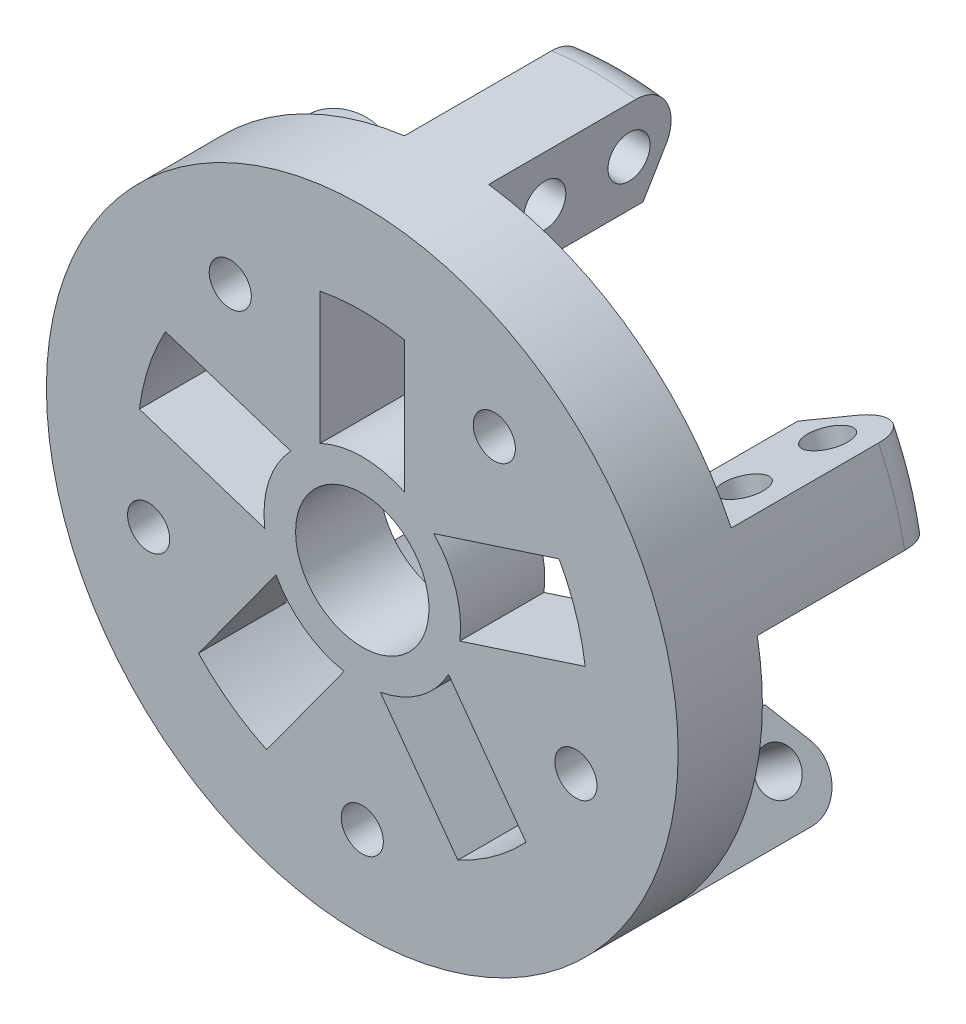
SolidWorks part; units mm, degrees
ref_plane "Front Plane" through (0, 0, 0) normal (0, 0, 1) x (1, 0, 0)
ref_plane "Top Plane" through (0, 0, 0) normal (0, 1, 0) x (1, 0, 0)
ref_plane "Right Plane" through (0, 0, 0) normal (1, 0, 0) x (0, 0, -1)
sketch "Sketch1" plane through (0, 0, 0) normal (0, 1, 0) x (1, 0, 0)
  line L1 (0, 0) -> (18918.9053, 0) construction
  line L2 (0, -1000) -> (0, 0) construction
  line L3 (0, 0) -> (-45, 0)
  line L4 (-45, 12) -> (-45, 33)
  line L5 (-37.4096, 37.2766) -> (-32, 34)
  line L6 (-32, 34) -> (-32, 12)
  line L7 (-32, 12) -> (0, 12)
  line L9 (-45, 12) -> (-45, 0)
  line L10 (0, 12) -> (0, 18918.9053) construction
  line L11 (0, 0) -> (0, 12)
  arc A0 (-45, 33) -> (-37.4096, 37.2766) centre (-40, 33) cw
  point P13 (0, 0)
  point P14 (0, 0)
  point P16 (0, 0)
  point P17 (-39.4291, 35.6602)
  point P18 (-37.9417, 36.7748)
  dimension "D1" = 5
  dimension "D2" = 32
  dimension "D3" = 21
  dimension "D4" = 22
  dimension "D5" = 90
  dimension "D6" = 12
revolve "Revolve1" add sketch "Sketch1" angle 360 about L10
sketch "Sketch2" plane through (0, 0, -12) normal (0, 0, -1) x (-1, 0, 0)
  line L0 (0, 0) -> (0, 32) construction
  line L1 (0, 0) -> (30.4338, 9.8885) construction
  line L2 (0, 0) -> (18.8091, -25.8885) construction
  line L3 (0, 0) -> (-18.8091, -25.8885) construction
  line L4 (0, 0) -> (-30.4338, 9.8885) construction
  line L5 (-2.5809, -13.7601) -> (-21.3601, -39.6074)
  line L6 (2.5809, -13.7601) -> (21.3601, -39.6074)
  line L7 (-13.8841, -1.7975) -> (-44.2695, 8.0753)
  line L8 (-12.2891, -6.7066) -> (-31.0683, -32.554)
  line L9 (-6, 12.6491) -> (-6, 44.5982)
  line L10 (-10.1759, 9.6151) -> (-40.5613, 19.4879)
  line L11 (10.1759, 9.6151) -> (40.5613, 19.4879)
  line L12 (6, 12.6491) -> (6, 44.5982)
  line L13 (12.2891, -6.7066) -> (31.0683, -32.554)
  line L14 (13.8841, -1.7975) -> (44.2695, 8.0753)
  circle A0 centre (0, 0) radius 32 construction
  circle A1 centre (0, 0) radius 32 construction
  circle A2 centre (0, 0) radius 45 construction
  arc A3 (-44.2695, 8.0753) -> (-31.0683, -32.554) centre (0, 0) ccw
  arc A4 (-13.8841, -1.7975) -> (-12.2891, -6.7066) centre (0, 0) ccw
  arc A5 (-6, 44.5982) -> (-40.5613, 19.4879) centre (0, 0) ccw
  arc A6 (40.5613, 19.4879) -> (6, 44.5982) centre (0, 0) ccw
  arc A7 (31.0683, -32.554) -> (44.2695, 8.0753) centre (0, 0) ccw
  arc A8 (-21.3601, -39.6074) -> (21.3601, -39.6074) centre (0, 0) ccw
  arc A9 (-6, 12.6491) -> (-10.1759, 9.6151) centre (0, 0) ccw
  arc A10 (10.1759, 9.6151) -> (6, 12.6491) centre (0, 0) ccw
  arc A11 (12.2891, -6.7066) -> (13.8841, -1.7975) centre (0, 0) ccw
  arc A12 (-2.5809, -13.7601) -> (2.5809, -13.7601) centre (0, 0) ccw
  point P2 (2.5809, -13.7601)
  dimension "D2" = 28
  dimension "D3" = 12
  dimension "D4" = 12
  dimension "D5" = 5
  dimension "D1" = 5
extrude "Cut-Extrude2" cut sketch "Sketch2" along normal through all
sketch "Sketch3" plane through (0, 0, -12) normal (0, 0, -1) x (-1, 0, 0)
  line L0 (0, -26) -> (0, -32) construction
  line L1 (-40.5613, 19.4879) -> (-28.04, 15.4195) construction
  line L2 (-6, 31.4325) -> (-6, 44.5982) construction
  line L3 (-40.5613, 19.4879) -> (-28.04, 15.4195)
  line L4 (-6, 31.4325) -> (-6, 44.5982)
  line L5 (0, 0) -> (0, -32) construction
  line L6 (0, 0) -> (-30.4338, -9.8885) construction
  line L7 (0, 0) -> (-18.8091, 25.8885) construction
  line L8 (0, 0) -> (18.8091, 25.8885) construction
  line L9 (0, 0) -> (30.4338, -9.8885) construction
  circle A0 centre (0, 0) radius 32 construction
  circle A1 centre (0, -32) radius 6
  circle A2 centre (0, -32) radius 3
  dimension "D1" = 64
  dimension "D2" = 12
  dimension "D3" = 6
  dimension "D4" = 5
extrude "Cut-Extrude3" cut sketch "Sketch3" against normal blind 6 contours A1 A2 region at (5.8303, -32, -12)
extrude "Cut-Extrude4" cut sketch "Sketch3<3>" against normal through all both and the other way through all contours A2 region at (0, -32, -12)
sketch "Sketch3<3>" plane through (0, 0, -12) normal (0, 0, -1) x (-1, 0, 0) same geometry as "Sketch3"
pattern_circular "CirPattern2" count 5 over 360 about axis through (0, 0, -12) along (0, 0, -1) of "Cut-Extrude4", "Cut-Extrude3"
sketch "Sketch4" plane through (0, 0, -12) normal (0, 0, -1) x (-1, 0, 0)
  line L0 (2.5809, -13.7601) -> (13.6214, -28.9561)
  line L4 (12.2891, -6.7066) -> (23.3296, -21.9027)
  line L5 (21.3601, -39.6074) -> (13.6214, -28.9561) construction
  line L6 (23.3296, -21.9027) -> (31.0683, -32.554) construction
  line L7 (21.3601, -39.6074) -> (13.6214, -28.9561)
  line L8 (23.3296, -21.9027) -> (31.0683, -32.554)
  circle A0 centre (0, 0) radius 9.5
  circle A2 centre (0, 0) radius 14
  arc A4 (13.6214, -28.9561) -> (23.3296, -21.9027) centre (0, 0) ccw construction
  arc A5 (13.6214, -28.9561) -> (23.3296, -21.9027) centre (0, 0) ccw
  point P7 (0, 0)
  point P12 (23.3758, -21.9662)
  dimension "D1" = 19
  dimension "D2" = 28
extrude "Cut-Extrude5" cut sketch "Sketch4" against normal through all both and the other way through all contours A0 region at (0, 0, -12)
extrude "Cut-Extrude6" cut sketch "Sketch4<4>" against normal through all both and the other way through all contours A2 L0 L4 region at (-13.3319, -18.3498, -12)
sketch "Sketch4<4>" plane through (0, 0, -12) normal (0, 0, -1) x (-1, 0, 0) same geometry as "Sketch4"
pattern_circular "CirPattern3" count 5 over 360 about axis through (0, 0, -12) along (0, 0, -1) of "Cut-Extrude6"
sketch "Sketch6" plane through (4.8541, -3.5267, 0) normal (0.809, -0.5878, 0) x (0, 0, -1)
  line L1 (0, 45) -> (0, -45) construction
  line L2 (0, 0) -> (41.3328, 0) construction
  circle A0 centre (20, -38) radius 3
  circle A1 centre (32, -38) radius 3
  dimension "D3" = 6
  dimension "D1" = 12
  dimension "D2" = 20
  dimension "D4" = 38
sketch "Sketch7" plane through (4.8541, -3.5267, 0) normal (0.809, -0.5878, 0) x (0, 0, -1)
  line L0 (0, 0) -> (58.474, 0) construction
extrude "Cut-Extrude7" cut sketch "Sketch6" against normal through all both and the other way through all contours A0 | A1 region at (-17.4817, -34.2694, -20) region at (-17.4817, -34.2694, -32)
pattern_circular "CirPattern4" count 5 over 360 about axis through (0, 0, -12) along (0, 0, -1) of "Cut-Extrude7"
